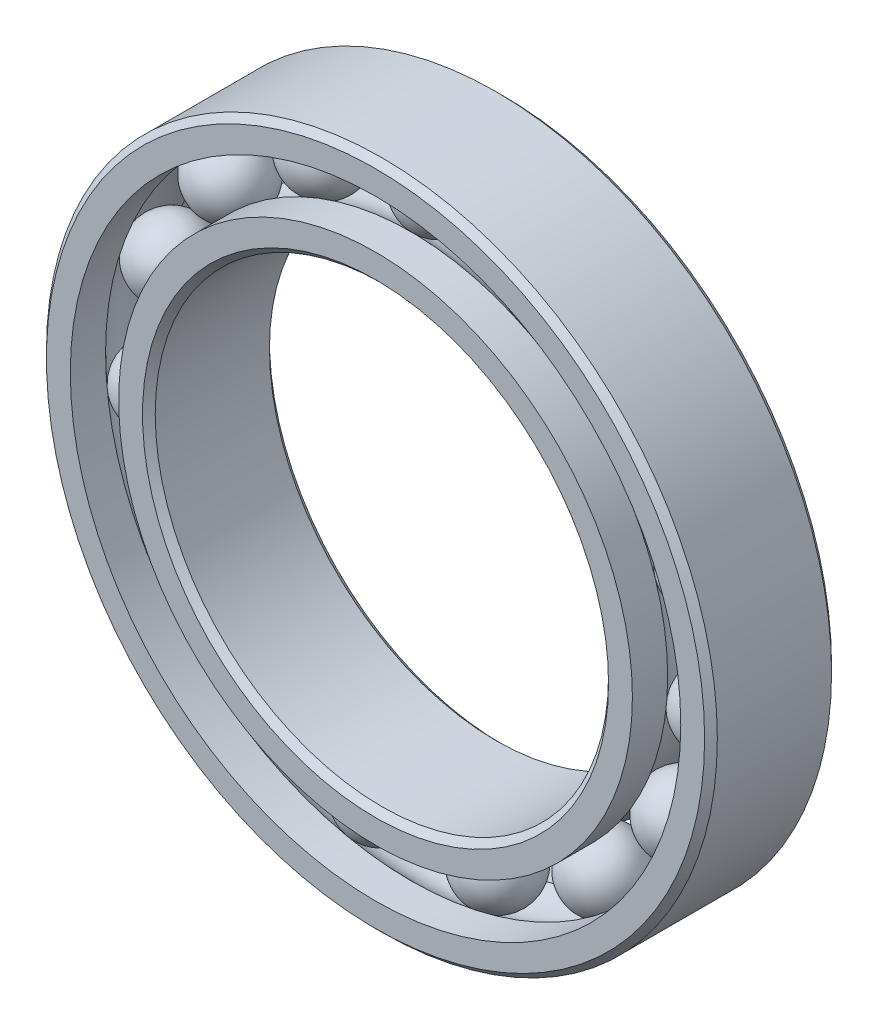
SolidWorks part; units mm, degrees
ref_plane "Front Plane" through (0, 0, 0) normal (0, 0, 1) x (1, 0, 0)
ref_plane "Top Plane" through (0, 0, 0) normal (0, 1, 0) x (1, 0, 0)
ref_plane "Right Plane" through (0, 0, 0) normal (1, 0, 0) x (0, 0, -1)
sketch "Sketch1" plane through (0, 0, 0) normal (0, 0, 1) x (1, 0, 0)
  circle A0 centre (0, 0) radius 18.5
  circle A1 centre (0, 0) radius 12.5
  dimension "OD" = 37
  dimension "ID" = 25
sketch "Sketch5" plane through (0, 0, 0) normal (1, 0, 0) x (0, 0, -1)
  line L0 (-3.5, 0) -> (3.5, 0) construction
  line L1 (0, 18.5) -> (0, -18.5) construction
  line L2 (3.15, 18.5) -> (-3.15, 18.5)
  line L3 (-3.15, 18.5) -> (-3.5, 18.15)
  line L4 (-3.5, 18.15) -> (-3.5, 16.8333)
  line L5 (-3.5, 16.8333) -> (-1.5556, 16.8333)
  line L6 (3.5, 16.8333) -> (1.5556, 16.8333)
  line L7 (3.5, 18.15) -> (3.5, 16.8333)
  line L8 (3.15, 18.5) -> (3.5, 18.15)
  line L9 (0, 18.5) -> (0, 15.5) construction
  line L10 (0, 15.5) -> (0, 12.5) construction
  line L11 (-2.0488, 15.5) -> (-3.5, 15.5) construction
  line L12 (2.5839, 14.1921) -> (2.9649, 14.1921) construction
  line L13 (-2.5839, 14.1921) -> (-2.9649, 14.1921) construction
  line L14 (-2.5839, 14.1921) -> (-2.5839, 16.8079) construction
  line L15 (-2.5839, 16.8079) -> (-2.9649, 16.8079) construction
  line L16 (-2.9649, 14.1921) -> (-2.9649, 16.8079) construction
  line L17 (-2.5839, 14.1921) -> (-2.9649, 16.8079) construction
  line L18 (-2.5839, 16.8079) -> (-2.9649, 14.1921) construction
  line L19 (2.9649, 14.1921) -> (2.9649, 16.8079) construction
  line L20 (2.5839, 16.8079) -> (2.9649, 16.8079) construction
  line L21 (2.5839, 14.1921) -> (2.5839, 16.8079) construction
  line L22 (0, 18.5) -> (0, -18.5) construction
  arc A0 (-1.5556, 16.8333) -> (1.5556, 16.8333) centre (0, 15.5) cw
  circle A1 centre (0, 15.5) radius 2.0488 construction
  point P14 (0, 12.5)
  point P15 (-2.7744, 15.5)
  dimension "Width" = 7
  dimension "D1" = 45
  dimension "D2" = 0.35
  dimension "D3" = 3.1111
  dimension "D4" = 1.3333
  dimension "D5" = 0.381
  dimension "D6" = 0.0254
  dimension "D7" = 7
revolve "Revolve1" add sketch "Sketch5" angle 360 about L0
sketch "Sketch3" plane through (0, 0, 0) normal (1, 0, 0) x (0, 0, -1)
  line L0 (-3.5, 14.1667) -> (-1.5556, 14.1667)
  line L1 (0, 18.5) -> (0, -18.5) construction
  line L2 (-3.5, 18.15) -> (-3.5, 16.8333) construction
  line L3 (-3.5, 14.1667) -> (-3.5, 12.85)
  line L4 (-3.15, 18.5) -> (-3.5, 18.15) construction
  line L5 (-3.5, 12.85) -> (-3.15, 12.5)
  line L6 (-3.15, 12.5) -> (3.15, 12.5)
  line L7 (3.15, 18.5) -> (3.15, -18.5) construction
  line L8 (3.15, 12.5) -> (3.5, 12.85)
  line L9 (3.5, -18.15) -> (3.5, 18.15) construction
  line L10 (3.5, 12.85) -> (3.5, 14.1667)
  line L11 (3.5, 14.1667) -> (1.5556, 14.1667)
  line L13 (3.15, 18.5) -> (3.5, 18.15) construction
  arc A0 (1.5556, 16.8333) -> (-1.5556, 16.8333) centre (0, 15.5) ccw construction
  arc A1 (1.5556, 14.1667) -> (-1.5556, 14.1667) centre (0, 15.5) cw
revolve "Revolve3" add sketch "Sketch3" angle 360 about L0
sketch "Sketch4" plane through (0, 0, 0) normal (1, 0, 0) x (0, 0, -1)
  line L0 (-2.0488, 15.5) -> (2.0488, 15.5)
  arc A2 (-2.0488, 15.5) -> (2.0488, 15.5) centre (0, 15.5) cw
  arc A3 (1.5556, 16.8333) -> (-1.5556, 16.8333) centre (0, 15.5) ccw construction
revolve "Revolve4" add sketch "Sketch4" angle 360 about L0
pattern_circular "CirPattern1" count 15 every 24 of bodies 104
ref_axis "Center Axis 1" through (0, 0, -3.15) along (0, 0, 1)
equation "\"D2@Sketch5\" = \"Width@Sketch5\" * .05"
equation "\"D3@Sketch5\" = \"Width@Sketch5\" / 2.25"
equation "\"D4@Sketch5\"=((\"OD@Sketch1\"-\"ID@Sketch1\")/2)/4.5"
equation "\"D2@CirPattern1\" = 360/\"Balls@CirPattern1\""
